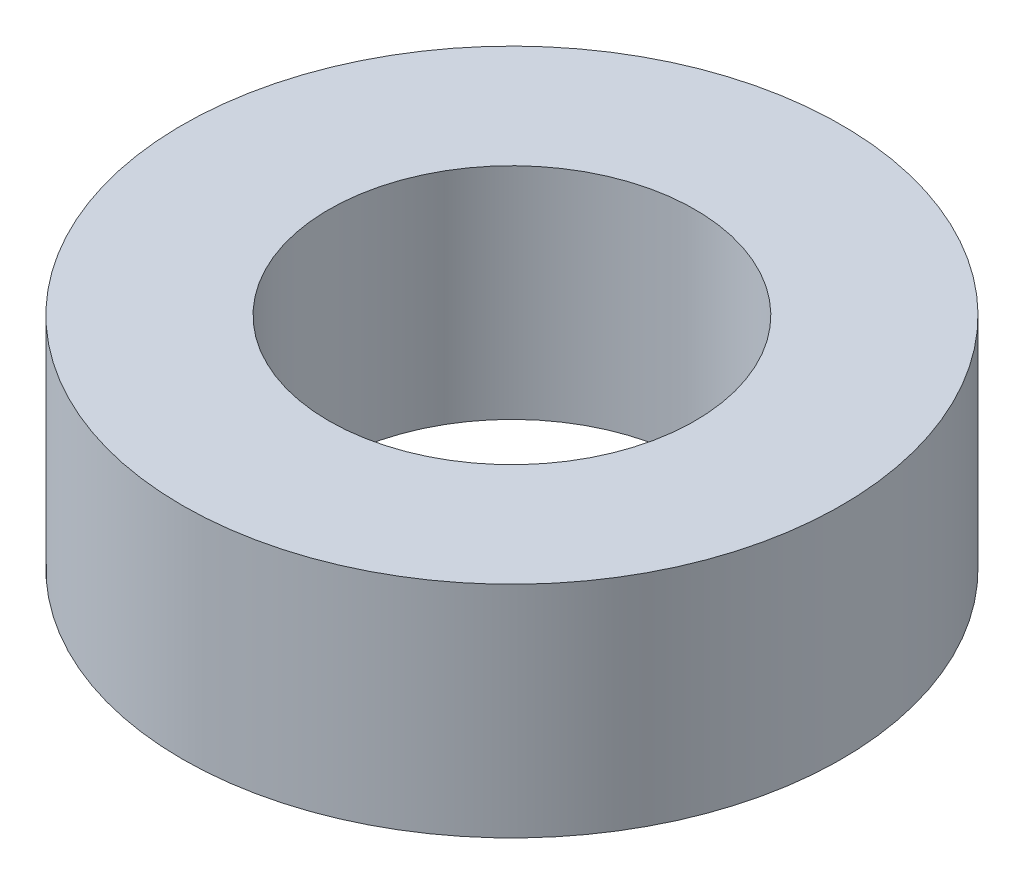
SolidWorks part; units mm, degrees
ref_plane "Front Plane" through (0, 0, 0) normal (0, 0, 1) x (1, 0, 0)
ref_plane "Top Plane" through (0, 0, 0) normal (0, 1, 0) x (1, 0, 0)
ref_plane "Right Plane" through (0, 0, 0) normal (1, 0, 0) x (0, 0, -1)
sketch "Sketch1" plane through (0, 0, 0) normal (0, 1, 0) x (1, 0, 0)
  circle A0 centre (0, 0) radius 45
  dimension "FLANGE_OD" = 90
extrude "Boss-Extrude1" add sketch "Sketch1" along normal blind 30
sketch "Sketch2" plane through (0, 0, 0) normal (0, 1, 0) x (1, 0, 0)
  circle A0 centre (0, 0) radius 25
  dimension "BORE_D" = 50
extrude "Cut-Extrude1" cut sketch "Sketch2" along normal through all
sketch "Sketch3" plane through (0, 30, 0) normal (0, 1, 0) x (1, 0, 0)
  circle A0 centre (0, 0) radius 18.8727 construction
  circle A1 centre (-18.8727, 0) radius 1.9826
  dimension "BOLT_D" = 3.9652
  dimension "BOLT_PCD" = 37.7454
extrude "Cut-Extrude2" cut sketch "Sketch3" against normal blind 18.6648 rebuild error yes
pattern_circular "CirPattern1" count 3 over 360 rebuild error yes
